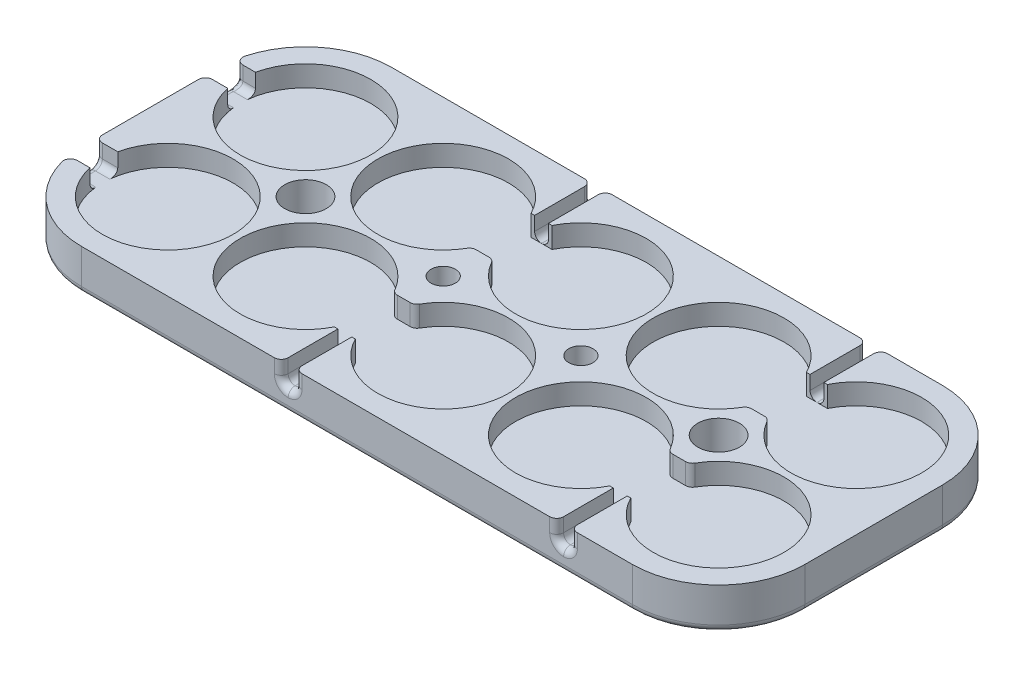
SolidWorks part; units mm, degrees
ref_plane "Front Plane" through (0, 0, 0) normal (0, 0, 1) x (1, 0, 0)
ref_plane "Top Plane" through (0, 0, 0) normal (0, 1, 0) x (1, 0, 0)
ref_plane "Right Plane" through (0, 0, 0) normal (1, 0, 0) x (0, 0, -1)
sketch "Sketch2" plane through (0, 0, 0) normal (0, 1, 0) x (1, 0, 0)
  line L0 (-39.7, 9.925) -> (-19.85, 9.925) construction
  line L1 (-19.85, 9.925) -> (0, 9.925) construction
  line L2 (0, 9.925) -> (19.85, 9.925) construction
  line L3 (19.85, 9.925) -> (39.7, 9.925) construction
  line L4 (39.7, 9.925) -> (39.7, -9.925) construction
  line L5 (39.7, -9.925) -> (19.85, -9.925) construction
  line L6 (19.85, -9.925) -> (0, -9.925) construction
  line L7 (0, -9.925) -> (-19.85, -9.925) construction
  line L8 (-39.7, 9.925) -> (-39.7, -9.925) construction
  line L9 (-39.7, -9.925) -> (-19.85, -9.925) construction
  line L10 (-39.7, 9.925) -> (39.7, -9.925) construction
  line L11 (-30.275, 9.925) -> (-29.275, 9.925) construction
  line L16 (-39.7, 0.5) -> (-39.7, -0.5) construction
  line L17 (-39.7, 22.35) -> (39.7, 22.35)
  line L19 (52.125, -9.925) -> (52.125, 9.925)
  line L20 (39.7, -22.35) -> (-39.7, -22.35)
  line L21 (-52.125, -9.925) -> (-52.125, 9.925)
  line L22 (-39.7, -9.925) -> (-52.125, -9.925) construction
  circle A0 centre (-39.7, 9.925) radius 9.425
  circle A1 centre (-19.85, 9.925) radius 9.425
  circle A2 centre (-39.7, -9.925) radius 9.425
  circle A3 centre (-19.85, -9.925) radius 9.425
  circle A4 centre (0, 9.925) radius 9.425
  circle A5 centre (0, -9.925) radius 9.425
  circle A6 centre (19.85, 9.925) radius 9.425
  circle A7 centre (19.85, -9.925) radius 9.425
  circle A8 centre (39.7, 9.925) radius 9.425
  circle A9 centre (39.7, -9.925) radius 9.425
  circle A10 centre (-39.7, 9.925) radius 12.425
  circle A11 centre (-39.7, -9.925) radius 12.425
  circle A12 centre (39.7, -9.925) radius 12.425
  circle A13 centre (39.7, 9.925) radius 12.425
  dimension "D1" = 18.85
  dimension "D2" = 1
  dimension "D3" = 1
  dimension "D4" = 3
extrude "Boss-Extrude1" add sketch "Sketch2" along normal blind 3 contours A13 L17 A10 A1 A11 A3 L20 A12 A7 A6 A5 A4 | A12 A13 A6 A8 | A13 A9 A12 A7 | A13 A12 L19 | A9 A13 A12 A8 | A11 A10 L21 | A11 A10 A1 A0 | A3 A11 A10 A2 | A10 A11 A0 A2 region at (-32.8744, 0, -19.9125) region at (0, 0, 0) region at (48.2539, 0, -18.4789) region at (-50.7094, 0, 0) region at (50.7094, 0, 0) region at (-50.5254, 0, 4.5259) region at (-39.7, 0, 0) region at (48.2539, 0, 18.4789) region at (39.7, 0, 0)
sketch "Sketch3" plane through (0, 0, 0) normal (0, 1, 0) x (1, 0, 0)
  line L0 (52.125, -9.925) -> (52.125, 9.925) construction
  line L1 (-52.125, -22.35) -> (52.125, -22.35)
  line L2 (-52.125, -22.35) -> (-52.125, 22.35)
  line L3 (-52.125, 22.35) -> (52.125, 22.35)
  line L4 (52.125, -22.35) -> (52.125, 22.35)
  line L5 (-52.125, -9.925) -> (-52.125, 9.925) construction
  line L6 (39.7, -22.35) -> (-39.7, -22.35) construction
  line L7 (-39.7, 22.35) -> (39.7, 22.35) construction
  circle A0 centre (-39.7, -9.925) radius 12.425
  circle A1 centre (-39.7, 9.925) radius 12.425
  circle A2 centre (39.7, 9.925) radius 12.425
  circle A3 centre (39.7, -9.925) radius 12.425
  circle A4 centre (-39.7, 9.925) radius 9.425 construction
  arc A5 (-39.7, 22.35) -> (-52.125, 9.925) centre (-39.7, 9.925) ccw construction
  arc A6 (-52.125, -9.925) -> (-39.7, -22.35) centre (-39.7, -9.925) ccw construction
  arc A7 (39.7, -22.35) -> (52.125, -9.925) centre (39.7, -9.925) ccw construction
  arc A8 (52.125, 9.925) -> (39.7, 22.35) centre (39.7, 9.925) ccw construction
extrude "Boss-Extrude2" add sketch "Sketch3" against normal blind 3 contours A3 A2 L3 A1 A0 L1 | A1 A0 | A0 A1 | A0 A1 | A1 L2 A0 | A3 A2 | A2 A3 | A3 A2 | A3 L4 A2 region at (0, 0, 0) region at (-39.7, 0, 11.0895) region at (-50.7094, 0, 0) region at (39.7, 0, 11.0895) region at (-39.7, 0, -11.0895) region at (-39.7, 0, 0) region at (39.7, 0, 0) region at (39.7, 0, -11.0895) region at (50.7094, 0, 0)
sketch "Sketch4" plane through (0, 0, 0) normal (0, 1, 0) x (1, 0, 0)
  line L1 (39.7, -5.675) -> (19.85, -5.675)
  line L2 (39.7, -5.675) -> (39.7, -14.175)
  line L3 (39.7, -14.175) -> (19.85, -14.175)
  line L4 (19.85, -5.675) -> (19.85, -14.175)
  line L5 (0, -5.675) -> (-19.85, -5.675)
  line L6 (0, -5.675) -> (0, -14.175)
  line L7 (0, -14.175) -> (-19.85, -14.175)
  line L8 (-19.85, -5.675) -> (-19.85, -14.175)
  line L13 (-19.85, 14.175) -> (0, 14.175)
  line L14 (-19.85, 14.175) -> (-19.85, 5.675)
  line L15 (-19.85, 5.675) -> (0, 5.675)
  line L16 (0, 14.175) -> (0, 5.675)
  line L17 (19.85, 14.175) -> (39.7, 14.175)
  line L18 (19.85, 14.175) -> (19.85, 5.675)
  line L19 (19.85, 5.675) -> (39.7, 5.675)
  line L20 (39.7, 14.175) -> (39.7, 5.675)
  circle A2 centre (-19.85, -9.925) radius 9.425 construction
  circle A3 centre (0, -9.925) radius 9.425 construction
  circle A4 centre (19.85, -9.925) radius 9.425 construction
  circle A5 centre (39.7, -9.925) radius 9.425 construction
  circle A6 centre (39.7, 9.925) radius 9.425 construction
  circle A7 centre (19.85, 9.925) radius 9.425 construction
  circle A8 centre (-19.85, 9.925) radius 9.425 construction
  circle A9 centre (0, 9.925) radius 9.425 construction
  point P26 (-19.85, -9.925)
  point P29 (0, -9.925)
  point P34 (19.85, -9.925)
  point P35 (39.7, -9.925)
  point P40 (39.7, 9.925)
  point P41 (19.85, 9.925)
  point P46 (-19.85, 9.925)
  point P47 (0, 9.925)
  dimension "D1" = 8.5
extrude "Cut-Extrude1" cut sketch "Sketch4" along normal through all
sketch "Sketch5" plane through (0, 0, 0) normal (0, 1, 0) x (1, 0, 0)
  line L0 (-52.125, -9.925) -> (-52.125, 9.925) construction
  line L1 (-10.925, 10.675) -> (-8.925, 10.675)
  line L2 (-10.925, 10.675) -> (-10.925, 22.35)
  line L3 (-10.925, 22.35) -> (-8.925, 22.35)
  line L4 (-8.925, 10.675) -> (-8.925, 22.35)
  line L5 (28.775, 10.675) -> (30.775, 10.675)
  line L6 (28.775, 10.675) -> (28.775, 22.35)
  line L7 (28.775, 22.35) -> (30.775, 22.35)
  line L8 (30.775, 10.675) -> (30.775, 22.35)
  line L9 (28.775, -10.675) -> (30.775, -10.675)
  line L10 (28.775, -10.675) -> (28.775, -22.35)
  line L11 (28.775, -22.35) -> (30.775, -22.35)
  line L12 (30.775, -10.675) -> (30.775, -22.35)
  line L13 (-10.925, -10.675) -> (-8.925, -10.675)
  line L14 (-10.925, -10.675) -> (-10.925, -22.35)
  line L15 (-10.925, -22.35) -> (-8.925, -22.35)
  line L16 (-8.925, -10.675) -> (-8.925, -22.35)
  line L17 (-44.7, -11.925) -> (-52.125, -11.925)
  line L18 (-44.7, -11.925) -> (-44.7, -7.925)
  line L19 (-44.7, -7.925) -> (-52.125, -7.925)
  line L20 (-52.125, -11.925) -> (-52.125, -7.925)
  line L21 (-39.7, 22.35) -> (39.7, 22.35) construction
  line L22 (39.7, -22.35) -> (-39.7, -22.35) construction
  line L23 (-39.7, -9.925) -> (-44.7, -9.925) construction
  line L24 (-44.7, 7.925) -> (-52.125, 7.925)
  line L25 (-44.7, 7.925) -> (-44.7, 11.925)
  line L26 (-44.7, 11.925) -> (-52.125, 11.925)
  line L27 (-52.125, 7.925) -> (-52.125, 11.925)
  line L28 (-39.7, 9.925) -> (-44.7, 9.925) construction
  line L29 (-9.925, 10.675) -> (-9.925, 5.675) construction
  line L30 (-11.4376, 5.675) -> (-8.4124, 5.675) construction
  line L31 (29.775, 5.675) -> (29.775, 10.675) construction
  line L32 (28.2624, 5.675) -> (31.2876, 5.675) construction
  line L33 (-9.925, -10.675) -> (-9.925, -5.675) construction
  line L34 (-8.4124, -5.675) -> (-11.4376, -5.675) construction
  line L35 (29.775, -5.675) -> (29.775, -10.675) construction
  line L36 (31.2876, -5.675) -> (28.2624, -5.675) construction
  dimension "D1" = 4
  dimension "D2" = 5
  dimension "D3" = 5
  dimension "D4" = 2
extrude "Cut-Extrude2" cut sketch "Sketch5" along normal through all
sketch "Sketch7" plane through (0, 0, 0) normal (0, 1, 0) x (1, 0, 0)
  line L0 (-29.775, 0) -> (-9.925, 0) construction
  line L1 (-9.925, 0) -> (9.925, 0) construction
  line L2 (9.925, 0) -> (29.775, 0) construction
  circle A1 centre (-29.775, 0) radius 3
  circle A2 centre (-9.925, 0) radius 1.75
  circle A3 centre (9.925, 0) radius 1.75
  circle A4 centre (29.775, 0) radius 3
  circle A5 centre (-29.775, 0) radius 4.6111 construction
  arc A6 (-11.4376, -5.675) -> (-11.4376, -14.175) centre (-19.85, -9.925) ccw construction
  circle A7 centre (-39.7, 9.925) radius 9.425 construction
  dimension "D1" = 6
  dimension "D2" = 3.5
extrude "Cut-Extrude3" cut sketch "Sketch7" along normal through all both and the other way through all
sketch "Sketch8" plane through (0, -3, 0) normal (0, -1, 0) x (1, 0, 0)
  circle A0 centre (9.925, 0) radius 3
  circle A1 centre (-9.925, 0) radius 3
  circle A2 centre (-9.925, 0) radius 1.75 construction
  circle A3 centre (9.925, 0) radius 1.75 construction
  circle A4 centre (29.775, 0) radius 3 construction
extrude "Cut-Extrude4" cut sketch "Sketch8" against normal blind 3.5
fillet "Fillet1" radius 1 40 edges at (28.775, 1.5, 22.35) (30.775, 1.5, 22.35) (-10.925, 1.5, 22.35) (-8.925, 1.5, 22.35) (-52.125, 1.5, 7.925) (-8.925, 1.5, -22.35) (-10.925, 1.5, -22.35) (30.775, 1.5, -22.35) (28.775, 1.5, -22.35) (29.775, 0, 22.35) (28.775, 0, 18.2625) (30.775, 0, 18.2625) (-9.925, 0, 22.35) (-8.925, 0, 18.2625) (-10.925, 0, 18.2625) (-50.4367, 0, 11.925) (-50.5177, 0, 7.925) (-52.125, 0, 8.925) (-9.925, 0, -22.35) (-10.925, 0, -18.2625) (-8.925, 0, -18.2625) (29.775, 0, -22.35) (28.775, 0, -18.2625) (30.775, 0, -18.2625) (28.2624, 1.5, 5.675) (31.2876, 1.5, 5.675) (-8.4124, 1.5, 5.675) (-11.4376, 1.5, 5.675) (-11.4376, 1.5, -5.675) (-8.4124, 1.5, -5.675) (28.2624, 1.5, -5.675) (31.2876, 1.5, -5.675) (-51.963, 1.5, 11.925) (-52.0844, 0, 10.9283) (-52.125, 1.5, -7.925) (-51.963, 1.5, -11.925) (-52.125, 0, -8.925) (-52.0844, 0, -10.9283) (-50.5177, 0, -7.925) (-50.4367, 0, -11.925)
fillet "Fillet2" radius 1 8 edges at (-48.4858, -3, 18.7108) (-52.125, -3, 0) (-48.4858, -3, -18.7108) (0, -3, -22.35) (48.4858, -3, -18.7108) (52.125, -3, 0) (48.4858, -3, 18.7108) (0, -3, 22.35)
sketch "Sketch9" plane through (0, -3, 0) normal (0, -1, 0) x (1, 0, 0)
  line L0 (-48.5919, 6.8) -> (-30.8081, 6.8) construction
  line L2 (-28.7419, 13.05) -> (8.8919, 13.05) construction
  line L4 (10.9581, 13.05) -> (48.5919, 13.05) construction
  line L5 (-48.5919, -13.05) -> (-30.8081, -13.05) construction
  line L6 (-28.7419, -13.05) -> (8.8919, -13.05) construction
  line L8 (10.9581, -13.05) -> (48.5919, -13.05) construction
  line L10 (-48.5919, 13.05) -> (-30.8081, 13.05) construction
  line L11 (-39.7, 13.05) -> (-39.7, 6.8) construction
  line L12 (-48.5919, -6.8) -> (-30.8081, -6.8) construction
  line L13 (-39.7, -6.8) -> (-39.7, -13.05) construction
  circle A0 centre (39.7, 9.925) radius 9.425 construction
  circle A1 centre (19.85, 9.925) radius 9.425 construction
  circle A2 centre (0, 9.925) radius 9.425 construction
  circle A3 centre (-19.85, 9.925) radius 9.425 construction
  circle A4 centre (-39.7, 9.925) radius 9.425 construction
  circle A5 centre (-39.7, -9.925) radius 9.425 construction
  circle A6 centre (-19.85, -9.925) radius 9.425 construction
  circle A7 centre (0, -9.925) radius 9.425 construction
  circle A8 centre (19.85, -9.925) radius 9.425 construction
  circle A9 centre (39.7, -9.925) radius 9.425 construction
  arc A10 (-48.9104, 7.925) -> (-48.9104, 11.925) centre (-39.7, 9.925) ccw construction
  text T0 "<b>B+</b>" font "Arial Rounded MT Bold" height 6.5
  text T1 "<b>B-</b>" font "Arial Rounded MT Bold" height 6.5
  text T2 "<b>2+</b>" font "Arial Rounded MT Bold" height 6.5
  text T4 "<b>4+</b>" font "Arial Rounded MT Bold" height 6.5
  text T7 "<b>8+</b>" font "Arial Rounded MT Bold" height 6.5
  text T9 "<b>6+</b>" font "Arial Rounded MT Bold" height 6.5
  dimension "D1" = 6.25
  dimension "D2" = 6.25
extrude "Cut-Extrude5" cut sketch "Sketch9" against normal blind 0.5
